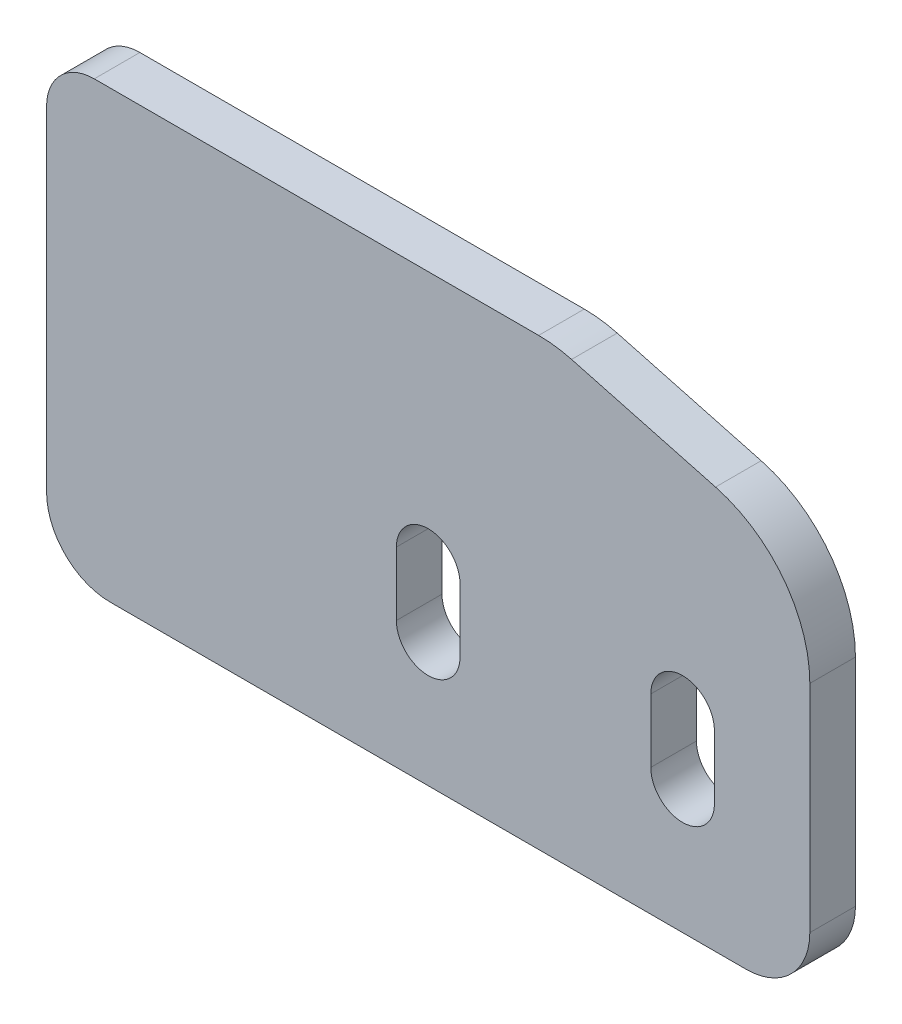
SolidWorks part; units mm, degrees
material "SS 304 (Default)"
ref_plane "Front Plane" through (0, 0, 0) normal (0, 0, 1) x (1, 0, 0)
ref_plane "Top Plane" through (0, 0, 0) normal (0, 1, 0) x (1, 0, 0)
ref_plane "Right Plane" through (0, 0, 0) normal (1, 0, 0) x (0, 0, -1)
sketch "Sketch1" plane through (0, 0, 0) normal (0, 0, 1) x (1, 0, 0)
  line L1 (38.1, 22.225) -> (-38.1, 22.225)
  line L2 (38.1, 22.225) -> (38.1, -22.225)
  line L3 (38.1, -22.225) -> (-38.1, -22.225)
  line L4 (-38.1, 22.225) -> (-38.1, -22.225)
  line L5 (38.1, 22.225) -> (-38.1, -22.225) construction
  line L6 (38.1, -22.225) -> (-38.1, 22.225) construction
  point P0 (0, 0)
  dimension "D1" = 76.2
  dimension "D2" = 44.45
sheet metal parameters "Sheet-Metal1" thickness 4.5542 parameters "D1"=6.35
base flange "Base-Flange1" sketch "Sketch1" thickness 4.5542 reverse thickness direction yes parameters "D1"=6.35
sketch "Sketch2" plane through (0, 0, 4.5542) normal (0, 0, 1) x (1, 0, 0)
  line L0 (12.7, 22.225) -> (38.1, 15.4191)
  line L1 (38.1, 22.225) -> (-38.1, 22.225) construction
  line L2 (38.1, -22.225) -> (38.1, 22.225) construction
  line L3 (38.1, 15.4191) -> (38.1, 22.225)
  line L4 (38.1, 22.225) -> (12.7, 22.225)
  dimension "D1" = 25.4
  dimension "D2" = 15
extrude "Cut-Extrude1" cut sketch "Sketch2" against normal through all normal cut yes
fillet "Fillet1" radius 4.7625 1 edges at (-38.1, 22.225, 2.2771)
fillet "Fillet2" radius 12.7 2 edges at (38.1, 15.4191, 2.2771) (12.7, 22.225, 2.2771)
sketch "Sketch3" plane through (0, 0, 4.5542) normal (0, 0, 1) x (1, 0, 0)
  line L0 (0, -9.525) -> (25.4, -9.525) construction
  line L1 (38.1, -22.225) -> (38.1, 5.674) construction
  line L2 (-38.1, -22.225) -> (38.1, -22.225) construction
  circle A0 centre (0, -9.525) radius 3.175
  circle A1 centre (25.4, -9.525) radius 3.175
  dimension "D1" = 6.35
  dimension "D2" = 12.7
  dimension "D3" = 25.4
  dimension "D4" = 12.7
extrude "Cut-Extrude2" cut sketch "Sketch3" against normal through all normal cut yes
fillet "Fillet3" radius 6.35 2 edges at (38.1, -22.225, 2.2771) (-38.1, -22.225, 2.2771)
sketch "Sketch4" plane through (0, 0, 4.5542) normal (0, 0, 1) x (1, 0, 0)
  line L0 (0, -9.525) -> (0, -3.175) construction
  line L1 (-3.175, -9.525) -> (-3.175, -3.175)
  line L2 (3.175, -9.525) -> (3.175, -3.175)
  line L3 (25.4, -9.525) -> (25.4, -3.175) construction
  line L4 (22.225, -9.525) -> (22.225, -3.175)
  line L5 (28.575, -9.525) -> (28.575, -3.175)
  arc A0 (-3.175, -9.525) -> (3.175, -9.525) centre (0, -9.525) ccw
  arc A1 (3.175, -3.175) -> (-3.175, -3.175) centre (0, -3.175) ccw
  arc A2 (22.225, -9.525) -> (28.575, -9.525) centre (25.4, -9.525) ccw
  arc A3 (28.575, -3.175) -> (22.225, -3.175) centre (25.4, -3.175) ccw
  circle A4 centre (0, -9.525) radius 3.175 construction
  point P3 (0, -6.35)
  point P8 (25.4, -6.35)
  dimension "D1" = 6.35
extrude "Cut-Extrude3" cut sketch "Sketch4" against normal through all normal cut yes
flat pattern "Flat-Pattern1" [suppressed]
sketch "Bend-Lines1" plane through (0, 0, 0) normal (0, 1, 0) x (-1, 0, 0)
sketch3d "Bounding-Box1" [suppressed]
  line L0 (0, 44.45, 0) -> (76.2, 44.45, 0) construction
  line L1 (0, 0, 0) -> (76.2, 0, 0) construction
  line L2 (0, 44.45, 0) -> (0, 0, 0) construction
  line L3 (76.2, 44.45, 0) -> (76.2, 0, 0) construction
